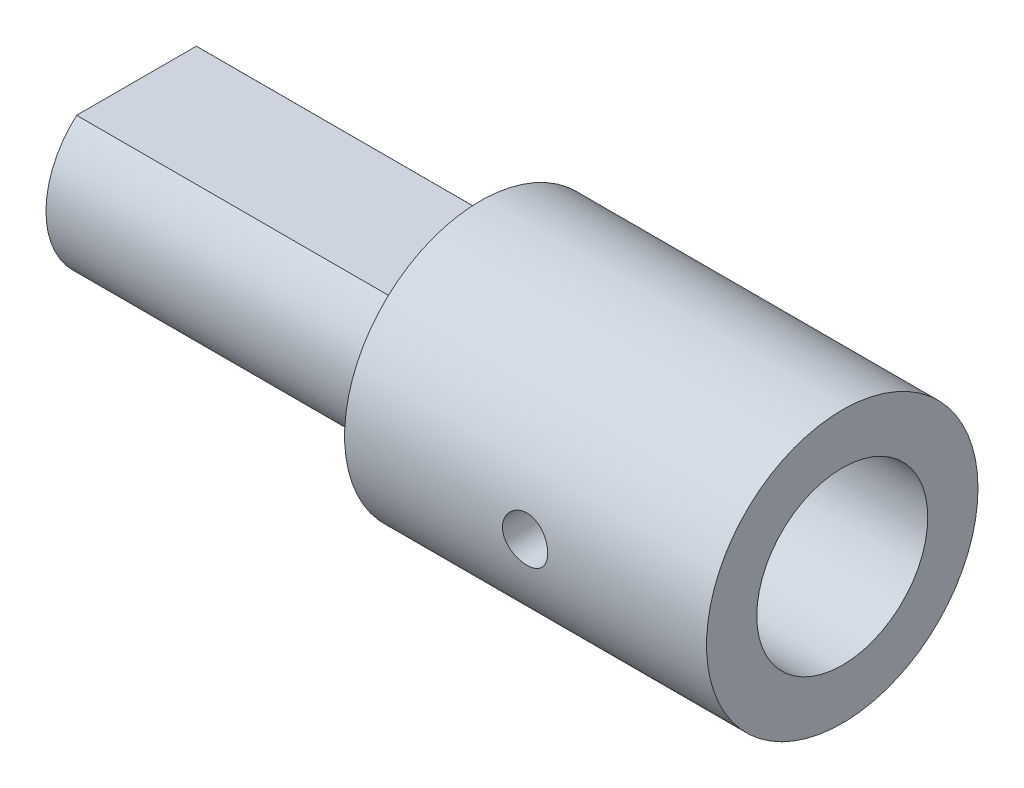
SolidWorks part; units mm, degrees
ref_plane "Front Plane" through (0, 0, 0) normal (1, 0, 0) x (0, 1, 0)
ref_plane "Top Plane" through (0, 0, 0) normal (0, 0, 1) x (0, 1, 0)
ref_plane "Right Plane" through (0, 0, 0) normal (0, 1, 0) x (-1, 0, 0)
sketch "Sketch1" plane through (0, 0, 0) normal (1, 0, 0) x (0, 1, 0)
  circle A0 centre (0, 0) radius 4.7625
  dimension "D1" = 9.525
extrude "Boss-Extrude1" add sketch "Sketch1" along normal blind 12.7
sketch "Sketch2" plane through (12.7, 0, 0) normal (1, 0, 0) x (0, 1, 0)
  circle A0 centre (0, 0) radius 3
  dimension "D1" = 6
extrude "Cut-Extrude1" cut sketch "Sketch2" against normal blind 9.5413
sketch "Sketch3" plane through (0, 0, 0) normal (-1, 0, 0) x (0, -1, 0)
  circle A0 centre (0, 0) radius 3.175
  dimension "D1" = 6.35
extrude "Boss-Extrude2" add sketch "Sketch3" along normal blind 12.065
sketch "Sketch4" plane through (0, 0, 0) normal (0, 0, 1) x (0, 1, 0)
  line L0 (0, -12.7) -> (0, -6.3337) construction
  line L1 (-4.7625, -12.7) -> (4.7625, -12.7) construction
  line L2 (0, 0) -> (0, -3.1587)
  line L3 (-3, -3.1587) -> (3, -3.1587) construction
  circle A0 centre (0, -6.3337) radius 0.7938
  point P1 (0, -6.3337)
  point P9 (0, 0)
  dimension "D2" = 1.5875
  dimension "D1" = 3.175
extrude "Cut-Extrude2" cut sketch "Sketch4" against normal blind 7.62 and the other way blind 7.62 contours A0
sketch "Sketch7" plane through (-12.065, 0, 0) normal (-1, 0, 0) x (0, -1, 0)
  line L1 (-2.3812, 2.1001) -> (-3.175, 2.1001)
  line L2 (-2.3812, 2.1001) -> (-2.3812, -2.1001)
  line L3 (-2.3812, -2.1001) -> (-3.175, -2.1001)
  line L4 (-3.175, 2.1001) -> (-3.175, -2.1001)
  circle A0 centre (0, 0) radius 3.175 construction
  circle A1 centre (0, 0) radius 3.175 construction
  point P9 (-3.175, 0)
  dimension "D1" = 0.7937
extrude "Cut-Extrude3" cut sketch "Sketch7" against normal blind 12.065
